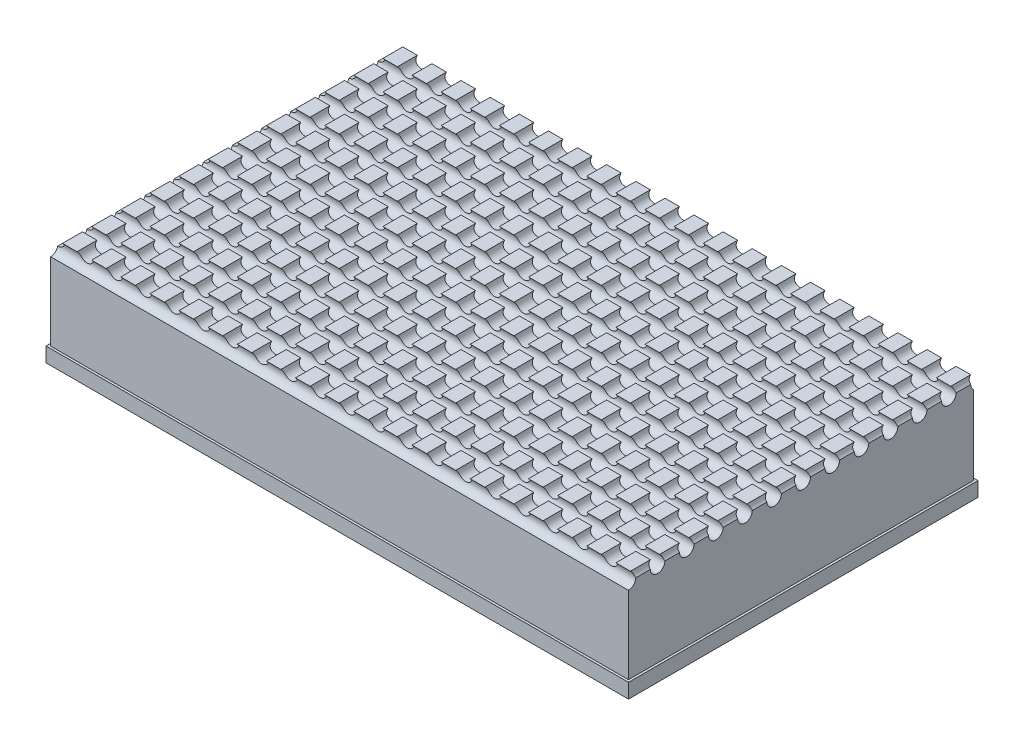
SolidWorks part; units mm, degrees
ref_plane "Front Plane" through (0, 0, 0) normal (0, 0, 1) x (1, 0, 0)
ref_plane "Top Plane" through (0, 0, 0) normal (0, 1, 0) x (1, 0, 0)
ref_plane "Right Plane" through (0, 0, 0) normal (1, 0, 0) x (0, 0, -1)
sketch "Sketch1" plane through (0, 0, 0) normal (0, 1, 0) x (1, 0, 0)
  line L1 (0, 0) -> (-127, 0)
  line L2 (0, 0) -> (0, 76.2)
  line L3 (0, 76.2) -> (-127, 76.2)
  line L4 (-127, 0) -> (-127, 76.2)
  dimension "D1" = 127
  dimension "D2" = 76.2
extrude "Boss-Extrude1" add sketch "Sketch1" along normal blind 3.175
sketch "Sketch3" plane through (0, 3.175, 0) normal (0, 1, 0) x (1, 0, 0)
  line L0 (-0.5, 75.7) -> (-126.5, 75.7)
  line L1 (-126.5, 75.7) -> (-126.5, 0.5)
  line L2 (-126.5, 0.5) -> (-0.5, 0.5)
  line L3 (-0.5, 0.5) -> (-0.5, 75.7)
extrude "Boss-Extrude4" add sketch "Sketch3" along normal blind 19.685
sketch "Sketch4" plane through (0, 0, -0.5) normal (0, 0, 1) x (1, 0, 0)
  circle A0 centre (-126.5, 22.86) radius 1.5875
  circle A1 centre (-120.15, 22.86) radius 1.5875
  circle A2 centre (-113.8, 22.86) radius 1.5875
  circle A3 centre (-107.45, 22.86) radius 1.5875
  circle A4 centre (-101.1, 22.86) radius 1.5875
  circle A5 centre (-94.75, 22.86) radius 1.5875
  circle A6 centre (-88.4, 22.86) radius 1.5875
  circle A7 centre (-82.05, 22.86) radius 1.5875
  circle A8 centre (-75.7, 22.86) radius 1.5875
  circle A9 centre (-69.35, 22.86) radius 1.5875
  circle A10 centre (-63, 22.86) radius 1.5875
  circle A11 centre (-56.65, 22.86) radius 1.5875
  circle A12 centre (-50.3, 22.86) radius 1.5875
  circle A13 centre (-43.95, 22.86) radius 1.5875
  circle A14 centre (-37.6, 22.86) radius 1.5875
  circle A15 centre (-31.25, 22.86) radius 1.5875
  circle A16 centre (-24.9, 22.86) radius 1.5875
  circle A17 centre (-18.55, 22.86) radius 1.5875
  circle A18 centre (-12.2, 22.86) radius 1.5875
  circle A19 centre (-5.85, 22.86) radius 1.5875
  circle A20 centre (0.5, 22.86) radius 1.5875
  dimension "D1" = 3.175
  dimension "D2" = 21
extrude "Cut-Extrude1" cut sketch "Sketch4" against normal through all
sketch "Sketch5" plane through (-0.5, 0, 0) normal (1, 0, 0) x (0, 0, -1)
  circle A0 centre (0.5, 21.6271) radius 1.5875
  circle A1 centre (6.85, 21.6271) radius 1.5875
  circle A2 centre (13.2, 21.6271) radius 1.5875
  circle A3 centre (19.55, 21.6271) radius 1.5875
  circle A4 centre (25.9, 21.6271) radius 1.5875
  circle A5 centre (32.25, 21.6271) radius 1.5875
  circle A6 centre (38.6, 21.6271) radius 1.5875
  circle A7 centre (44.95, 21.6271) radius 1.5875
  circle A8 centre (51.3, 21.6271) radius 1.5875
  circle A9 centre (57.65, 21.6271) radius 1.5875
  circle A10 centre (64, 21.6271) radius 1.5875
  circle A11 centre (70.35, 21.6271) radius 1.5875
  circle A12 centre (76.7, 21.6271) radius 1.5875
  dimension "D1" = 13
extrude "Cut-Extrude2" cut sketch "Sketch5" against normal through all
